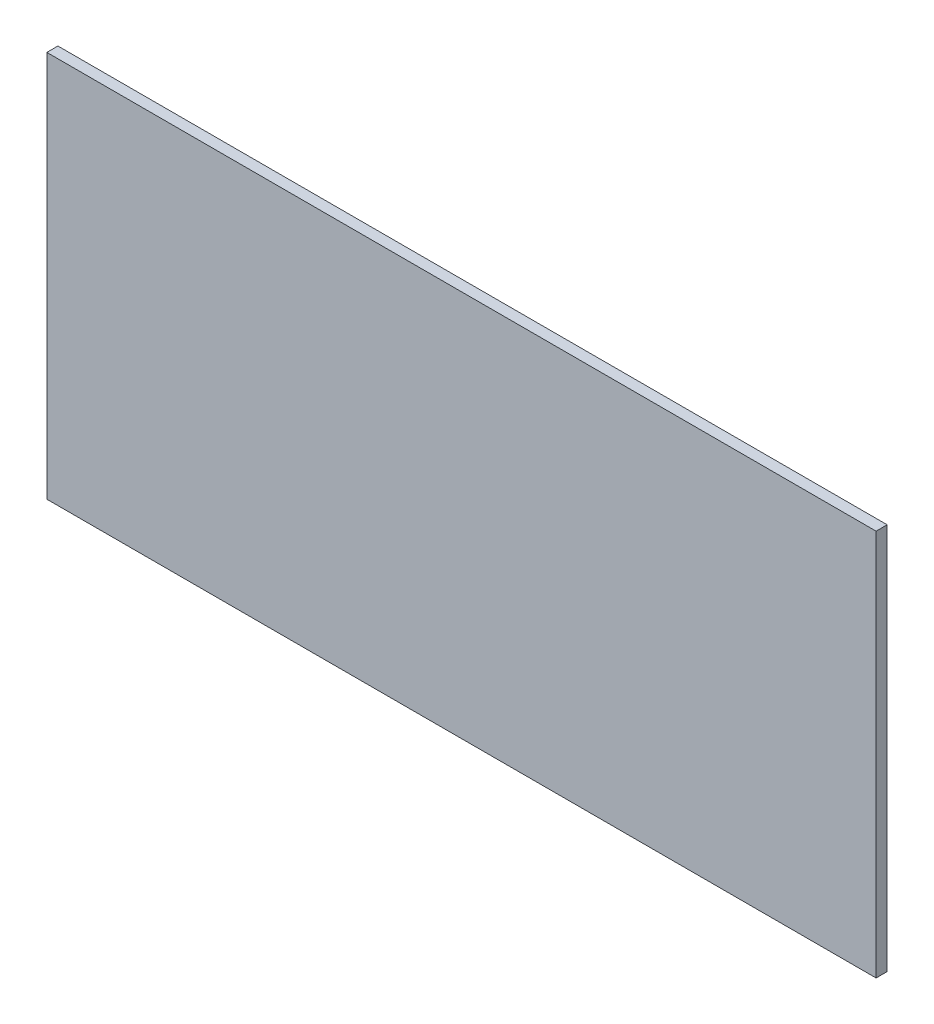
SolidWorks part; units mm, degrees
material "Brass"
ref_plane "Front Plane" through (0, 0, 0) normal (0, 0, 1) x (1, 0, 0)
ref_plane "Top Plane" through (0, 0, 0) normal (0, 1, 0) x (1, 0, 0)
ref_plane "Right Plane" through (0, 0, 0) normal (1, 0, 0) x (0, 0, -1)
sketch "Sketch1" plane through (0, 0, 0) normal (0, 0, 1) x (1, 0, 0)
  line L0 (0, 0) -> (300, 0)
  line L1 (300, 0) -> (300, 140)
  line L2 (300, 140) -> (0, 140)
  line L3 (0, 140) -> (0, 0)
extrude "Boss-Extrude1" add sketch "Sketch1" along normal blind 4
sketch "Sketch2" plane through (0, 0, 0) normal (0, 0, 1) x (1, 0, 0)
  circle A0 centre (15, 15) radius 1.5
  circle A1 centre (15, 124) radius 1.5
  circle A2 centre (287, 15) radius 1.5
  circle A3 centre (287, 124) radius 1.5
  dimension "D1" = 3
  dimension "D2" = 3
  dimension "D3" = 3
  dimension "D4" = 3
extrude "Cut-Extrude1" cut sketch "Sketch2" against normal mid plane 7
